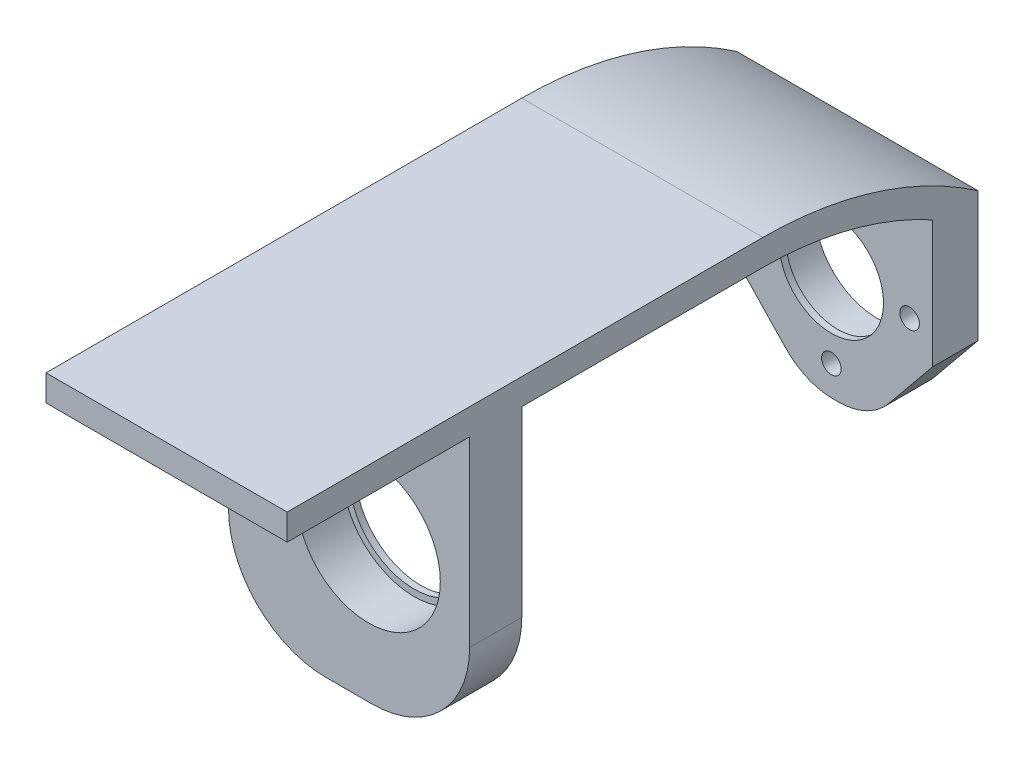
SolidWorks part; units mm, degrees
ref_plane "Front Plane" through (0, 0, 0) normal (0, 0, 1) x (1, 0, 0)
ref_plane "Top Plane" through (0, 0, 0) normal (0, 1, 0) x (1, 0, 0)
ref_plane "Right Plane" through (0, 0, 0) normal (1, 0, 0) x (0, 0, -1)
sketch "Sketch3" plane through (0, 0, 0) normal (1, 0, 0) x (0, 0, -1)
  line L0 (0, 0) -> (73, 0)
  line L1 (0, 0) -> (0, -4)
  line L2 (0, -4) -> (73, -4)
  line L4 (113.6909, -22.5) -> (70.143, -22.5) construction
  line L6 (90.9961, -30.5) -> (104.9961, -30.5) construction
  line L7 (90.9961, -30.5) -> (90.9961, -14.5) construction
  line L8 (90.9961, -14.5) -> (104.9961, -14.5) construction
  line L9 (104.9961, -30.5) -> (104.9961, -14.5) construction
  line L10 (90.9961, -30.5) -> (104.9961, -14.5) construction
  line L11 (90.9961, -14.5) -> (104.9961, -30.5) construction
  line L13 (109.8205, -18.5) -> (115.4706, -18.5)
  arc A0 (73, 0) -> (115.4706, -18.5) centre (73, -58) cw
  arc A1 (73, -4) -> (104.9961, -14.5) centre (73, -58) cw
  arc A2 (104.9961, -14.5) -> (109.8205, -18.5) centre (73, -58) cw
  point P9 (97.9961, -22.5)
  dimension "D1" = 58
  dimension "D2" = 4
  dimension "D3" = 73
  dimension "D4" = 22.5
  dimension "D5" = 16
  dimension "D6" = 4
  dimension "D7" = 14
extrude "Boss-Extrude1" add sketch "Sketch3" along normal blind 37
ref_plane "Plane1" through (21.5, 0, 0) normal (1, 0, 0) x (0, 0, -1)
sketch "Sketch4" plane through (37, 0, 0) normal (1, 0, 0) x (0, 0, -1)
  line L0 (28, -4) -> (28, -14.5)
  line L1 (0, -4) -> (73, -4) construction
  line L2 (114.75, -23.7518) -> (114.75, -33.7153) construction
  line L3 (0, 0) -> (0, -4) construction
  line L4 (28, -4) -> (36, -4)
  line L5 (36, -4) -> (36, -15.5)
  line L6 (36, -15.5) -> (35, -15.5) construction
  line L7 (35, -15.5) -> (35, -14.5) construction
  line L8 (35, -14.5) -> (28, -14.5) construction
  line L9 (35, -15.5) -> (35, -25.5) construction
  line L10 (35, -25.5) -> (17.1507, -25.5) construction
  line L11 (28, -14.5) -> (28, -36.5)
  line L12 (36, -15.5) -> (36, -35.5)
  line L13 (28, -47) -> (36, -47)
  line L14 (28, -47) -> (28, -36.5)
  line L15 (36, -47) -> (36, -35.5)
  line L16 (73, 0) -> (0, 0) construction
  arc A0 (109.8205, -18.5) -> (73, -4) centre (73, -58) ccw construction
  point P22 (28, -25.5)
  point P23 (36, -25.5)
  dimension "D1" = 28
  dimension "D2" = 114.75
  dimension "D3" = 25.5
  dimension "D4" = 8
  dimension "D5" = 7
  dimension "D6" = 11.5
  dimension "D7" = 11
extrude "Boss-Extrude3" add sketch "Sketch4" against normal up to surface (37 mm away) contours L11 L14 L13 L15 L12 L5 L4 L0 up to face at (0, -6.1802, -62.4324)
sketch "Sketch5" plane through (0, 0, -28) normal (0, 0, 1) x (1, 0, 0)
  line L0 (37, -25.5) -> (21.5, -25.5) construction
  line L1 (37, -47) -> (37, -4) construction
  circle A0 centre (21.5, -25.5) radius 11
  dimension "D2" = 22
  dimension "D1" = 15.5
  dimension "D3" = 21.5
extrude "Cut-Extrude1" cut sketch "Sketch5" against normal blind 7
sketch "Sketch6" plane through (0, 0, -35) normal (0, 0, 1) x (1, 0, 0)
  circle A0 centre (21.5, -25.5) radius 10
  dimension "D1" = 20
extrude "Cut-Extrude2" cut sketch "Sketch6" against normal blind 7
sketch "Sketch7" plane through (37, 0, 0) normal (1, 0, 0) x (0, 0, -1)
  line L0 (36, -4) -> (99, -4) construction
  line L1 (99, -4) -> (99, -10.6714) construction
  line L2 (67.5, -4) -> (67.5, -25.5) construction
  line L3 (67.5, -25.5) -> (116.1248, -25.5) construction
  line L4 (99, -10.6714) -> (99, -16) construction
  line L5 (99, -16) -> (105, -16) construction
  line L6 (105, -16) -> (105, -17.5) construction
  line L7 (105, -17.5) -> (106, -17.5) construction
  line L8 (106, -17.5) -> (106, -15.2566) construction
  line L9 (99, -10.6714) -> (99, -47)
  line L10 (99, -47) -> (106, -47)
  line L11 (106, -47) -> (106, -15.2566)
  arc A0 (109.8205, -18.5) -> (73, -4) centre (73, -58) ccw construction
  arc A2 (106, -15.2566) -> (99, -10.6714) centre (73, -58) ccw
  dimension "D1" = 63
  dimension "D2" = 21.5
  dimension "D3" = 9.5
  dimension "D4" = 8
  dimension "D5" = 6
  dimension "D6" = 1
  dimension "D7" = 43
extrude "Boss-Extrude4" add sketch "Sketch7" against normal up to surface (37 mm away) contours L11 A2 L9 L10 up to face at (0, -13.9081, -50.2594)
sketch "Sketch8" plane through (0, 0, -106) normal (0, 0, 1) x (1, 0, 0)
  circle A0 centre (21.5, -25.5) radius 9.5
  dimension "D1" = 19
extrude "Cut-Extrude3" cut sketch "Sketch8" along normal blind 6
sketch "Sketch9" plane through (0, 0, -100) normal (0, 0, -1) x (-1, 0, 0)
  circle A0 centre (-21.5, -25.5) radius 8
  dimension "D1" = 16
extrude "Cut-Extrude4" cut sketch "Sketch9" against normal blind 1
sketch "Sketch10" plane through (0, 0, -106) normal (0, 0, -1) x (-1, 0, 0)
  line L0 (0, -23.7577) -> (-17.4711, -42.0819)
  line L1 (0, -47) -> (0, -15.2566) construction
  line L2 (-17.4711, -42.0819) -> (-27.3185, -42.0819)
  line L3 (-27.3185, -42.0819) -> (-37, -30.2284)
  line L4 (-37, -47) -> (-37, -15.2566) construction
  line L5 (-37, -30.2284) -> (-37, -47)
  line L6 (-37, -47) -> (0, -47)
  line L7 (0, -47) -> (0, -23.7577)
extrude "Cut-Extrude5" cut sketch "Sketch10" against normal up to surface (7 mm away) up to face at (13.5, -25.5, -99)
sketch "Sketch11" plane through (37, 0, 0) normal (1, 0, 0) x (0, 0, -1)
  line L0 (106, -15.2566) -> (106, -10.303)
  line L1 (109.8205, -18.5) -> (115.4706, -18.5) construction
  line L2 (109.8205, -18.5) -> (115.4706, -18.5)
  arc A0 (115.4706, -18.5) -> (73, 0) centre (73, -58) ccw construction
  arc A1 (109.8205, -18.5) -> (106, -15.2566) centre (73, -58) ccw construction
  arc A2 (109.8205, -18.5) -> (106, -15.2566) centre (73, -58) ccw
  arc A3 (115.4706, -18.5) -> (106, -10.303) centre (73, -58) ccw
extrude "Cut-Extrude6" cut sketch "Sketch11" against normal through all
fillet "Fillet2" radius 10 2 edges at (17.4711, -42.0819, -102.5) (27.3185, -42.0819, -102.5)
sketch "Sketch12" plane through (0, 0, -99) normal (0, 0, 1) x (1, 0, 0)
  line L0 (21.5, -25.5) -> (21.5, -13.5) construction
  circle A0 centre (21.5, -13.5) radius 1.5
  circle A1 centre (33.5, -25.5) radius 1.5
  circle A2 centre (21.5, -37.5) radius 1.5
  circle A3 centre (9.5, -25.5) radius 1.5
  point P12 (21.5, -25.5)
  dimension "D1" = 3
  dimension "D3" = 12
  dimension "D4" = 12
  dimension "D5" = 12
  dimension "D2" = 4
extrude "Cut-Extrude7" cut sketch "Sketch12" against normal through all
sketch "Sketch13" [suppressed] plane through (0, 0, -28) normal (0, 0, 1) x (1, 0, 0)
  line L0 (23, 0) -> (23, -32) construction
  line L1 (37, 0) -> (0, 0) construction
  line L3 (0, -47) -> (0, -4) construction
  circle A0 centre (23, -32) radius 11
  dimension "D2" = 22
  dimension "D1" = 32
  dimension "D3" = 23
extrude "Cut-Extrude8" [suppressed] cut sketch "Sketch13" against normal blind 7 contours A0
sketch "Sketch14" [suppressed] plane through (0, 0, -35) normal (0, 0, 1) x (1, 0, 0)
  circle A0 centre (23, -32) radius 10
  dimension "D1" = 20
extrude "Cut-Extrude9" [suppressed] cut sketch "Sketch14" against normal blind 7
sketch "Sketch15" [suppressed] plane through (0, 0, 0) normal (-1, 0, 0) x (0, 0, 1)
  line L0 (-94, -8.2506) -> (-94, -47)
  line L1 (-94, -47) -> (-101, -47)
  line L2 (-101, -47) -> (-101, -11.8264)
  line L3 (-36, -4) -> (-36, -47) construction
  line L4 (-28, -47) -> (-36, -47) construction
  arc A0 (-73, -4) -> (-109.8205, -18.5) centre (-73, -58) ccw construction
  arc A1 (-94, -8.2506) -> (-101, -11.8264) centre (-73, -58) ccw
  dimension "D1" = 58
  dimension "D2" = 7
extrude "Boss-Extrude5" [suppressed] add sketch "Sketch15" against normal up to surface (37 mm away) up to face at (37, -15.6062, -57.1006)
sketch "Sketch16" [suppressed] plane through (0, 0, -94) normal (0, 0, 1) x (1, 0, 0)
  circle A0 centre (23, -32) radius 8
  dimension "D1" = 16
extrude "Cut-Extrude10" [suppressed] cut sketch "Sketch16" against normal blind 1
sketch "Sketch17" [suppressed] plane through (0, 0, -95) normal (0, 0, 1) x (1, 0, 0)
  circle A0 centre (23, -32) radius 9.5
  dimension "D1" = 19
extrude "Cut-Extrude11" [suppressed] cut sketch "Sketch17" against normal through all
sketch "Sketch18" [suppressed] plane through (37, 0, 0) normal (1, 0, 0) x (0, 0, -1)
  line L0 (101, -11.8264) -> (101, -7.2063)
  line L1 (109.8205, -18.5) -> (115.4706, -18.5) construction
  line L2 (109.8205, -18.5) -> (115.4706, -18.5)
  arc A0 (115.4706, -18.5) -> (73, 0) centre (73, -58) ccw construction
  arc A1 (109.8205, -18.5) -> (101, -11.8264) centre (73, -58) ccw construction
  arc A2 (115.4706, -18.5) -> (101, -7.2063) centre (73, -58) ccw
  arc A3 (109.8205, -18.5) -> (101, -11.8264) centre (73, -58) ccw
extrude "Cut-Extrude12" [suppressed] cut sketch "Sketch18" against normal through all
sketch "Sketch19" [suppressed] plane through (0, 0, -101) normal (0, 0, -1) x (-1, 0, 0)
  line L0 (-23, -32) -> (-23, -20) construction
  circle A0 centre (-23, -20) radius 1.5
  circle A1 centre (-11, -32) radius 1.5
  circle A2 centre (-23, -44) radius 1.5
  circle A3 centre (-35, -32) radius 1.5
  point P12 (-23, -32)
  dimension "D1" = 3
  dimension "D2" = 12
  dimension "D4" = 12
  dimension "D5" = 12
  dimension "D3" = 4
extrude "Cut-Extrude13" [suppressed] cut sketch "Sketch19" against normal up to surface (7 mm away)
fillet "Fillet3" [suppressed] radius 10
fillet "Fillet4" [suppressed] radius 10
fillet "Fillet5" radius 15 2 edges at (0, -47, -32) (37, -47, -32)
equation "\"mini-flipper-shaft-diameter\"= 26mm"
equation "\"mini-shaft-ring-groove-diam\"= 7.8mm"
equation "\"mini-shaft-ring-groove-width\"= 1mm"
equation "\"dtCoverPlate-DistFrom-GearCent\"= 73mm"
equation "\"wormGearShaft-L\"= \"dtCoverPlate-DistFrom-GearCent\" - 27.75 + 3.75"
equation "\"wormGearShaft-Dsmall\"= 6mm"
equation "\"wormGearShaft-Dworm\"= 12mm"
equation "\"wormL-D\" = 12mm"
equation "\"wormR-D\" = 15mm"
equation "\"wormGearL-D\" = 40mm"
equation "\"wormGearR-D\" = 50mm"
